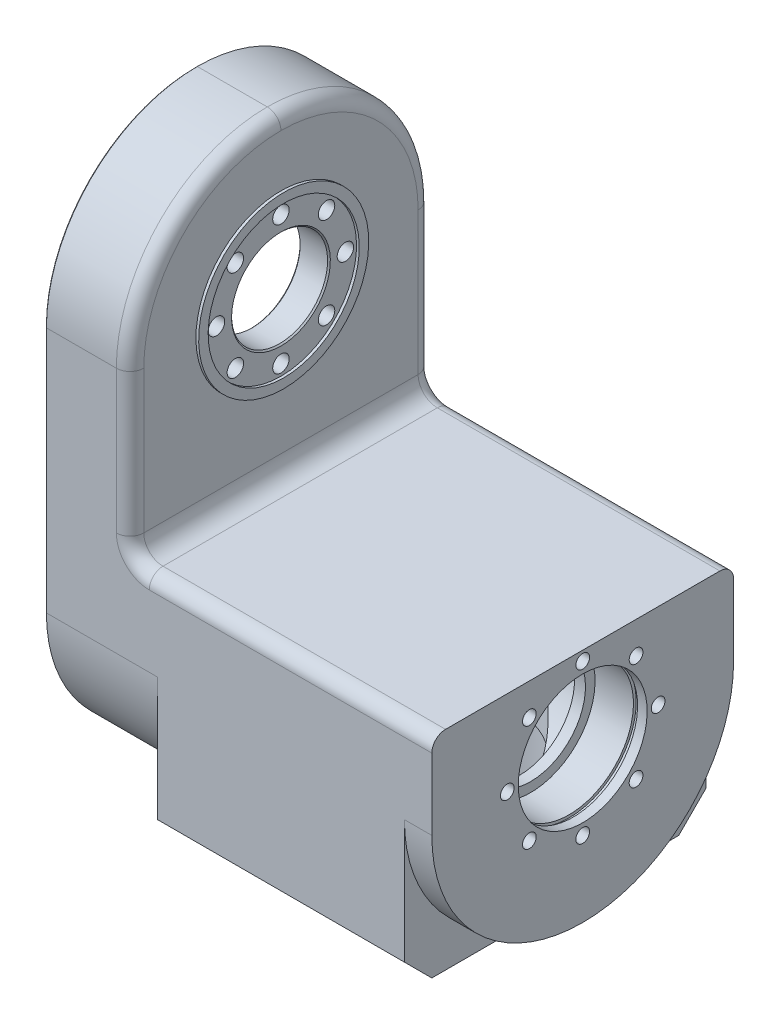
SolidWorks part; units mm, degrees
ref_plane "前视基准面" through (0, 0, 0) normal (0, 0, 1) x (1, 0, 0)
ref_plane "上视基准面" through (0, 0, 0) normal (0, 1, 0) x (1, 0, 0)
ref_plane "右视基准面" through (0, 0, 0) normal (1, 0, 0) x (0, 0, -1)
sketch "草图1" plane through (0, 0, 0) normal (0, 0, 1) x (1, 0, 0)
  line L0 (141, 0) -> (141, -200)
  line L1 (0, 0) -> (141, 0)
  line L2 (0, 0) -> (0, -200)
  line L3 (0, -200) -> (141, -200)
  dimension "D1" = 141
  dimension "D2" = 200
extrude "拉伸1" add sketch "草图1" along normal blind 110
fillet "圆角1" radius 55 2 edges at (70.5, 0, 0) (70.5, 0, 110)
sketch "草图2" plane through (0, 0, 0) normal (-1, 0, 0) x (0, 0, 1)
  circle A0 centre (55, -55) radius 47.75
  dimension "D1" = 95.5
extrude "切除-拉伸1" cut sketch "草图2" against normal blind 20
sketch "草图4" plane through (0, 0, 110) normal (0, 0, 1) x (1, 0, 0)
  line L0 (0, 0) -> (0, -55) construction
  line L1 (157.4229, 5.3768) -> (31, 5.3768)
  line L2 (157.4229, 5.3768) -> (157.4229, -114)
  line L3 (157.4229, -114) -> (31, -114)
  line L4 (31, 5.3768) -> (31, -114)
  line L6 (0, -200) -> (141, -200) construction
  dimension "D1" = 31
  dimension "D2" = 86
extrude "切除-拉伸3" cut sketch "草图4" against normal blind 125
fillet "圆角4" radius 55 2 edges at (70.5, -200, 110) (70.5, -200, 0)
sketch "草图9" plane through (0, 0, 0) normal (-1, 0, 0) x (0, 0, 1)
  circle A0 centre (55, -145) radius 47.75
  dimension "D1" = 95.5
extrude "切除-拉伸4" cut sketch "草图9" against normal blind 20
sketch "草图10" plane through (0, 0, 0) normal (-1, 0, 0) x (0, 0, 1)
  line L0 (7.25, -55) -> (7.25, -145)
  line L1 (7.25, -145) -> (102.75, -145)
  line L2 (102.75, -145) -> (102.75, -55)
  line L3 (102.75, -55) -> (7.25, -55)
  circle A0 centre (55, -55) radius 47.75 construction
  circle A1 centre (55, -55) radius 47.75 construction
  circle A2 centre (55, -145) radius 47.75 construction
  circle A3 centre (55, -145) radius 47.75 construction
extrude "切除-拉伸5" cut sketch "草图10" against normal blind 20
sketch "草图11" plane through (20, 0, 0) normal (-1, 0, 0) x (0, 0, 1)
  circle A0 centre (55, -55) radius 17.5
  dimension "D1" = 35
extrude "切除-拉伸6" cut sketch "草图11" against normal blind 25
chamfer "倒角1" distance 0.5 angle 45 6 edges at (0, -183.8909, 93.8909) (0, -100, 110) (0, -183.8909, 16.1091) (0, -16.1091, 93.8909) (0, -100, 0) (0, -16.1091, 16.1091)
sketch "草图16" plane through (20, 0, 0) normal (-1, 0, 0) x (0, 0, 1)
  circle A0 centre (55, -145) radius 27.5
  dimension "D1" = 55
extrude "切除-拉伸12" cut sketch "草图16" against normal blind 165
fillet "圆角6" radius 7 1 edges at (31, -114, 55)
ref_plane "基准面1" through (131, 0, 0) normal (1, 0, 0) x (0, 0, -1)
sketch "草图17" plane through (131, 0, 0) normal (1, 0, 0) x (0, 0, -1)
  line L0 (-110, -145) -> (-110, -114) construction
  line L1 (-110, -145) -> (0, -145)
  line L2 (-110, -145) -> (-110, -200)
  line L3 (-110, -200) -> (0, -200)
  line L4 (0, -145) -> (0, -200)
  arc A0 (-110, -145) -> (-55, -200) centre (-55, -145) ccw construction
extrude "拉伸2" add sketch "草图17" against normal blind 90
sketch "草图18" plane through (20, 0, 0) normal (-1, 0, 0) x (0, 0, 1)
  line L0 (27.5, -145) -> (82.5, -145) construction
  circle A0 centre (55, -145) radius 27.5
  dimension "D1" = 55
extrude "切除-拉伸13" cut sketch "草图18" against normal through all
sketch "草图19" plane through (0, -200, 0) normal (0, -1, 0) x (1, 0, 0)
  line L0 (41, 110) -> (41, 55) construction
  circle A0 centre (86, 55) radius 30
  dimension "D1" = 45
  dimension "D2" = 60
extrude "切除-拉伸14" cut sketch "草图19" against normal blind 50
sketch "草图21" plane through (20, 0, 0) normal (-1, 0, 0) x (0, 0, 1)
  circle A3 centre (55, -31.5) radius 3
  circle A4 centre (71.617, -38.383) radius 3
  circle A5 centre (78.5, -55) radius 3
  circle A6 centre (71.617, -71.617) radius 3
  circle A7 centre (55, -78.5) radius 3
  circle A8 centre (38.383, -71.617) radius 3
  circle A9 centre (31.5, -55) radius 3
  circle A10 centre (38.383, -38.383) radius 3
  dimension "D1" = 6
extrude "切除-拉伸16" cut sketch "草图21" against normal blind 30
sketch "草图22" plane through (20, 0, 0) normal (-1, 0, 0) x (0, 0, 1)
  circle A0 centre (55, -31.5) radius 5
  circle A1 centre (71.617, -38.383) radius 5
  circle A2 centre (78.5, -55) radius 5
  circle A3 centre (71.617, -71.617) radius 5
  circle A4 centre (55, -78.5) radius 5
  circle A5 centre (38.383, -71.617) radius 5
  circle A6 centre (31.5, -55) radius 5
  circle A7 centre (38.383, -38.383) radius 5
  dimension "D1" = 10
extrude "切除-拉伸17" cut sketch "草图22" against normal blind 6
sketch "草图24" plane through (31, 0, 0) normal (1, 0, 0) x (0, 0, -1)
  circle A0 centre (-55, -55) radius 31
  circle A10 centre (-55, -55) radius 27.55
  dimension "D1" = 62
  dimension "D2" = 55.1
extrude "拉伸3" add sketch "草图24" along normal blind 1
sketch "草图26" plane through (0, 0, 0) normal (-1, 0, 0) x (0, 0, 1)
  circle A0 centre (106, -145) radius 2
  circle A1 centre (106, -55) radius 2
  circle A5 centre (55, -4) radius 2
  circle A11 centre (4, -55) radius 2
  circle A12 centre (4, -145) radius 2
  circle A13 centre (55, -196) radius 2
extrude "切除-拉伸19" cut sketch "草图26" against normal blind 15
sketch "草图27" plane through (20, 0, 0) normal (-1, 0, 0) x (0, 0, 1)
  circle A0 centre (55, -145) radius 31
  dimension "D1" = 62
extrude "切除-拉伸20" cut sketch "草图27" against normal blind 10
sketch "草图28" plane through (141, 0, 0) normal (1, 0, 0) x (0, 0, -1)
  circle A0 centre (-55, -145) radius 27.5
  circle A1 centre (-55, -145) radius 23.5
extrude "拉伸4" add sketch "草图28" against normal blind 23
sketch "草图30" plane through (118, 0, 0) normal (-1, 0, 0) x (0, 0, 1)
  circle A0 centre (55, -145) radius 23.5
  circle A1 centre (55, -145) radius 20
  dimension "D1" = 40
extrude "拉伸5" add sketch "草图30" against normal blind 4
ref_plane "基准面2" through (136, 0, 0) normal (1, 0, 0) x (0, 0, -1)
sketch "草图31" plane through (136, 0, 0) normal (1, 0, 0) x (0, 0, -1)
  circle A0 centre (-55, -145) radius 24.5
  circle A1 centre (-55, -145) radius 23.5
  dimension "D1" = 47
  dimension "D2" = 49
extrude "切除-拉伸21" cut sketch "草图31" along normal blind 1.5
sketch "草图32" plane through (0, -200, 0) normal (0, -1, 0) x (1, 0, 0)
  circle A0 centre (86, 55) radius 34
  dimension "D1" = 68
extrude "切除-拉伸22" cut sketch "草图32" against normal blind 25
sketch "草图33" plane through (0, -200, 0) normal (0, -1, 0) x (1, 0, 0)
  circle A5 centre (86, 95) radius 2.5
  circle A6 centre (114.2843, 83.2843) radius 2.5
  circle A7 centre (126, 55) radius 2.5
  circle A8 centre (114.2843, 26.7157) radius 2.5
  circle A9 centre (86, 15) radius 2.5
  circle A10 centre (57.7157, 26.7157) radius 2.5
  circle A11 centre (46, 55) radius 2.5
  circle A12 centre (57.7157, 83.2843) radius 2.5
extrude "切除-拉伸23" cut sketch "草图33" against normal blind 15
chamfer "倒角2" distance 10 angle 45 2 edges at (86, -200, 0) (86, -200, 110)
sketch "草图34" plane through (141, 0, 0) normal (1, 0, 0) x (0, 0, -1)
  circle A1 centre (-55, -172.5) radius 2.5
  circle A2 centre (-74.4454, -164.4454) radius 2.5
  circle A3 centre (-82.5, -145) radius 2.5
  circle A4 centre (-74.4454, -125.5546) radius 2.5
  circle A5 centre (-55, -117.5) radius 2.5
  circle A6 centre (-35.5546, -125.5546) radius 2.5
  circle A7 centre (-27.5, -145) radius 2.5
  circle A8 centre (-35.5546, -164.4454) radius 2.5
  circle A9 centre (-55, -117.5) radius 2.5 [skipped]
  dimension "D1" = 5
extrude "切除-拉伸24" cut sketch "草图34" against normal blind 15
fillet "圆角7" radius 5 8 edges at (89.5, -114, 0) (33.0503, -111.9497, 0) (31, -81, 0) (31, -16.1091, 16.1091) (31, -16.1091, 93.8909) (31, -81, 110) (33.0503, -111.9497, 110) (89.5, -114, 110)
sketch "草图39" plane through (0, 0, 0) normal (0, 0, -1) x (-1, 0, 0)
  circle A0 centre (-86, -145) radius 5
extrude "切除-拉伸29" cut sketch "草图39" against normal blind 15
sketch "草图40" plane through (0, 0, 15) normal (0, 0, -1) x (-1, 0, 0)
  circle A0 centre (-86, -145) radius 2
extrude "切除-拉伸30" cut sketch "草图40" against normal blind 15
chamfer "倒角3" distance 0.5 angle 45 1 edges at (120, -200, 55)
chamfer "倒角4" distance 0.5 angle 45 2 edges at (30, -172.5, 55) (20, -176, 55)
chamfer "倒角5" distance 0.5 angle 45 2 edges at (20, -72.5, 55) (31, -72.5, 55)
sketch "草图43" plane through (0, 0, 0) normal (0, 0, -1) x (-1, 0, 0)
  line L0 (0, -55) -> (0, -145) construction
  circle A0 centre (-10, -100) radius 5
  dimension "D1" = 10
extrude "切除-拉伸32" cut sketch "草图43" against normal blind 10
